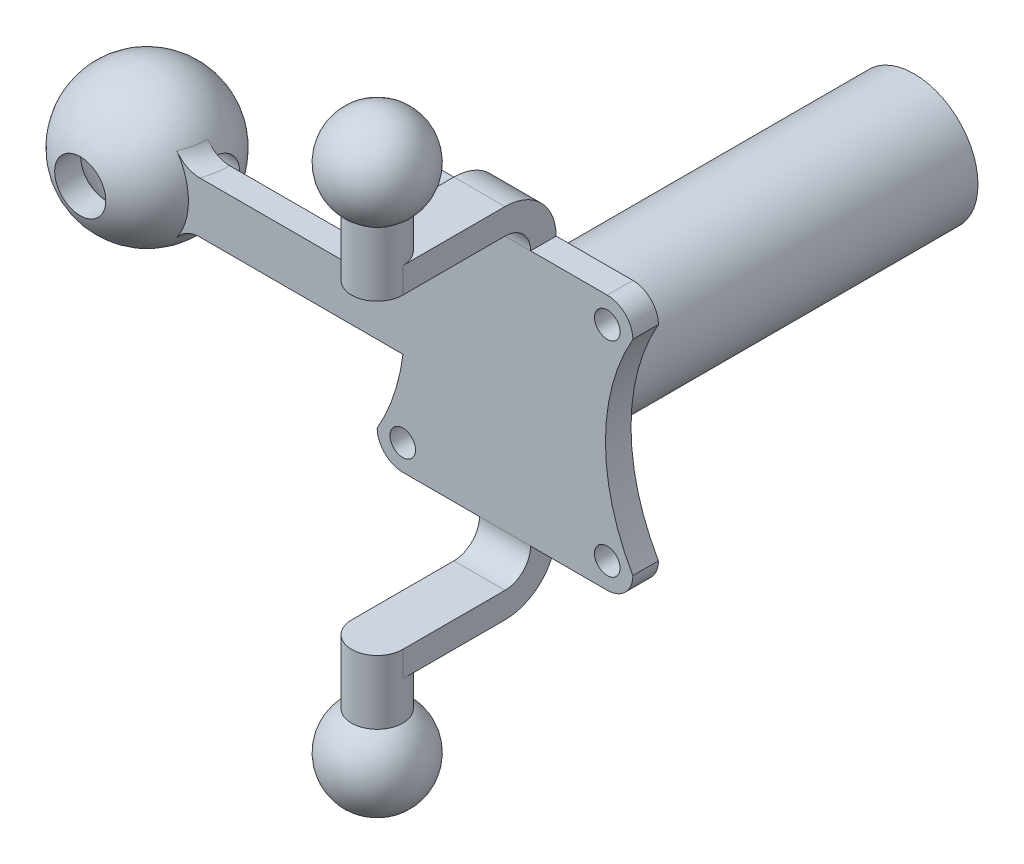
SolidWorks part; units mm, degrees
material "201 Annealed Stainless Steel (SS)"
ref_plane "Front Plane" through (0, 0, 0) normal (0, 0, 1) x (1, 0, 0)
ref_plane "Top Plane" through (0, 0, 0) normal (0, 1, 0) x (1, 0, 0)
ref_plane "Right Plane" through (0, 0, 0) normal (1, 0, 0) x (0, 0, -1)
sketch "Sketch2" plane through (0, 0, 0) normal (0, 0, 1) x (1, 0, 0)
  line L1 (-40, 50) -> (40, 50)
  line L2 (-50, 40) -> (-50, -40)
  line L3 (-40, -50) -> (40, -50)
  line L4 (50, 40) -> (50, -40)
  line L5 (-50, 50) -> (50, -50) construction
  line L6 (-50, -50) -> (50, 50) construction
  arc A0 (50, 40) -> (40, 50) centre (40, 40) ccw
  arc A1 (40, -50) -> (50, -40) centre (40, -40) ccw
  arc A2 (-50, 40) -> (-40, 50) centre (-40, 40) cw
  arc A3 (-50, -40) -> (-40, -50) centre (-40, -40) ccw
  point P0 (0, 0)
  dimension "D1" = 10
extrude "Boss-Extrude1" add sketch "Sketch2" along normal blind 10
sketch "Sketch3" plane through (0, 0, 10) normal (0, 0, 1) x (1, 0, 0)
  line L0 (-50, 40) -> (-50, -40) construction
  line L1 (-50, 40) -> (-50, -40)
  line L2 (50, 40) -> (50, -40)
  arc A0 (-50, 40) -> (-50, -40) centre (-119.282, 0) cw
  arc A1 (-50, -40) -> (-40, -50) centre (-40, -40) ccw construction
  arc A2 (50, 40) -> (50, -40) centre (119.282, 0) ccw
extrude "Cut-Extrude1" cut sketch "Sketch3" against normal blind 10
ref_plane "Plane1" through (-40, -50, 10) normal (1, 0, 0) x (0, 0, -1)
sketch "Sketch6" plane through (0, -50, 0) normal (0, -1, 0) x (1, 0, 0)
  line L1 (-40, 0) -> (40, 0) construction
  line L2 (-40, 10) -> (40, 10) construction
  line L3 (-10, 0) -> (10, 0)
  line L4 (-10, 0) -> (-10, 10)
  line L5 (-10, 10) -> (10, 10)
  line L6 (10, 0) -> (10, 10)
  point P0 (0, 0)
  point P1 (-10, 0)
extrude "Boss-Extrude5" add sketch "Sketch6" along normal blind 10
sketch "Sketch7" plane through (0, 0, 0) normal (0, 0, 1) x (1, 0, 0)
  line L1 (-10, -60) -> (10, -60)
  line L2 (-10, -60) -> (-10, -70)
  line L3 (-10, -70) -> (10, -70)
  line L4 (10, -60) -> (10, -70)
extrude "Boss-Extrude6" add sketch "Sketch7" along normal blind 60
fillet "Fillet7" radius 20 1 edges at (0, -70, 0)
fillet "Fillet8" radius 10 1 edges
sketch "Sketch8" plane through (0, -60, 0) normal (0, 1, 0) x (1, 0, 0)
  line L0 (10, -60) -> (-10, -60)
  arc A0 (-10, -60) -> (10, -60) centre (0, -60) ccw
extrude "Boss-Extrude7" add sketch "Sketch8" against normal blind 10
sketch "Sketch14" plane through (0, 0, 10) normal (0, 0, 1) x (1, 0, 0)
  line L0 (-39.282, 0) -> (39.282, 0)
  line L1 (-40, 50) -> (40, 50)
  arc A0 (-50, -40) -> (-50, 40) centre (-119.282, 0) ccw construction
  arc A1 (50, 40) -> (50, -40) centre (119.282, 0) ccw construction
  arc A2 (-40, 50) -> (-50, 40) centre (-40, 40) ccw construction
  arc A3 (50, 40) -> (40, 50) centre (40, 40) ccw construction
  spline S0 degree 2 poles (-39.282, 0) (-39.3595, 21.3507) (-50, 40) knots 0 0 0 1 1 1
  spline S1 degree 2 poles (-50, 40) (-49.1421, 49.1421) (-40, 50) knots 0 0 0 1 1 1
  spline S2 degree 2 poles (40, 50) (49.1421, 49.1421) (50, 40) knots 0 0 0 1 1 1
  spline S3 degree 2 poles (50, 40) (39.3595, 21.3507) (39.282, 0) knots 0 0 0 1 1 1
  point P8 (-41.5547, 18.9332)
  point P9 (-47.0711, 47.0711)
  point P16 (47.0711, 47.0711)
  point P26 (41.5547, 18.9332)
extrude "Cut-Extrude7" cut sketch "Sketch14" against normal blind 18
mirror "Mirror2" about plane through (-39.282, 0, -8) normal (0, -1, 0) of "Boss-Extrude7", "Boss-Extrude5", "Boss-Extrude6", "Fillet8", "Fillet7", "Cut-Extrude1", "Boss-Extrude1"
sketch "Sketch16" plane through (0, 0, 0) normal (0, 0, -1) x (-1, 0, 0)
  circle A0 centre (0, 0) radius 25
sketch "Sketch19" plane through (0, 0, 10) normal (0, 0, 1) x (1, 0, 0)
  circle A0 centre (-40, 40) radius 5
  circle A1 centre (40, 40) radius 5
  circle A2 centre (-40, -40) radius 5
  circle A3 centre (40, -40) radius 5
  point P0 (0, 0)
  point P1 (-40, 40)
  point P3 (-40, -40)
  point P5 (40, -40)
  point P7 (40, 40)
extrude "Cut-Extrude9" cut sketch "Sketch19" against normal blind 30
sketch "Sketch20" plane through (0, 0, 10) normal (0, 0, 1) x (1, 0, 0)
sketch "Sketch21" plane through (0, 0, 10) normal (0, 0, 1) x (1, 0, 0)
  line L0 (-133.2926, 10.9937) -> (0, 20)
  line L1 (-133.2926, -10.9937) -> (0, -20)
  arc A0 (0, -20) -> (0, 20) centre (0, 0) ccw
  circle A1 centre (-150, 0) radius 20
  point P7 (-150, 0)
sketch "Sketch29" plane through (0, 70, 0) normal (0, 1, 0) x (1, 0, 0)
  circle A0 centre (0, -60) radius 10
extrude "Boss-Extrude16" add sketch "Sketch29" along normal blind 15
sketch "Sketch30" plane through (0, 0, 0) normal (1, 0, 0) x (0, 0, -1)
  line L0 (-60, 85) -> (-60, 135) construction
  line L1 (-50, 85) -> (-70, 85) construction
  line L2 (-60, 118.0278) -> (-60, 85)
  line L3 (-60, 85) -> (-50, 85)
  arc A0 (-50, 85) -> (-60, 118.0278) centre (-60, 100) ccw
revolve "Revolve2" add sketch "Sketch30" angle 360 about L0
sketch "Sketch31" plane through (0, -70, 0) normal (0, -1, 0) x (1, 0, 0)
  circle A0 centre (0, 60) radius 10
extrude "Boss-Extrude17" add sketch "Sketch31" along normal blind 15
sketch "Sketch32" plane through (0, 0, 0) normal (1, 0, 0) x (0, 0, -1)
  line L0 (-60, -85) -> (-60, -135) construction
  line L1 (-70, -85) -> (-50, -85) construction
  line L2 (-60, -118.0278) -> (-60, -85)
  line L3 (-60, -85) -> (-70, -85)
  arc A0 (-70, -85) -> (-60, -118.0278) centre (-60, -100) ccw
  point P4 (-60, -100)
revolve "Revolve3" add sketch "Sketch32" angle 360 about L0
sketch "Sketch33" plane through (0, 0, 10) normal (0, 0, 1) x (1, 0, 0)
  line L0 (-134, 10) -> (-39.9095, 10)
  line L1 (-134, -10) -> (-39.9095, -10)
  line L5 (-134, -10) -> (-134, 10)
  arc A0 (-50, -40) -> (-50, 40) centre (-119.282, 0) ccw construction
  arc A1 (-39.9095, 10) -> (-39.9095, -10) centre (-119.282, 0) cw
  point P1 (0, 0)
extrude "Boss-Extrude21" add sketch "Sketch33" against normal blind 10
sketch "Sketch34" plane through (0, 0, 0) normal (0, 0, 1) x (1, 0, 0)
  line L0 (-134, 0) -> (-184, 0) construction
  line L1 (-134, 10) -> (-134, -10) construction
  line L2 (-178, 0) -> (-168.868, 0)
  line L3 (-134, 10) -> (-123.8466, 10)
  line L4 (-39.9095, 10) -> (-134, 10) construction
  arc A0 (-134, 10) -> (-168.868, 0) centre (-150, 0) ccw
  arc A1 (-123.8466, 10) -> (-178, 0) centre (-150, 0) ccw
  point P5 (-150, 0)
revolve "Revolve5" add sketch "Sketch34" angle 360 about L0
fillet "Fillet9" radius 10 1 edges at (-124.3482, 10, 5.0978)
fillet "Fillet10" radius 10 1 edges at (-124.3482, -10, 5.0978)
sketch "Sketch35" plane through (0, 0, 0) normal (0, 0, 1) x (1, 0, 0)
  circle A0 centre (-150, 0) radius 10
extrude "Cut-Extrude11" cut sketch "Sketch35" along normal blind 30
extrude "Boss-Extrude22" add sketch "Sketch16" along normal blind 150
